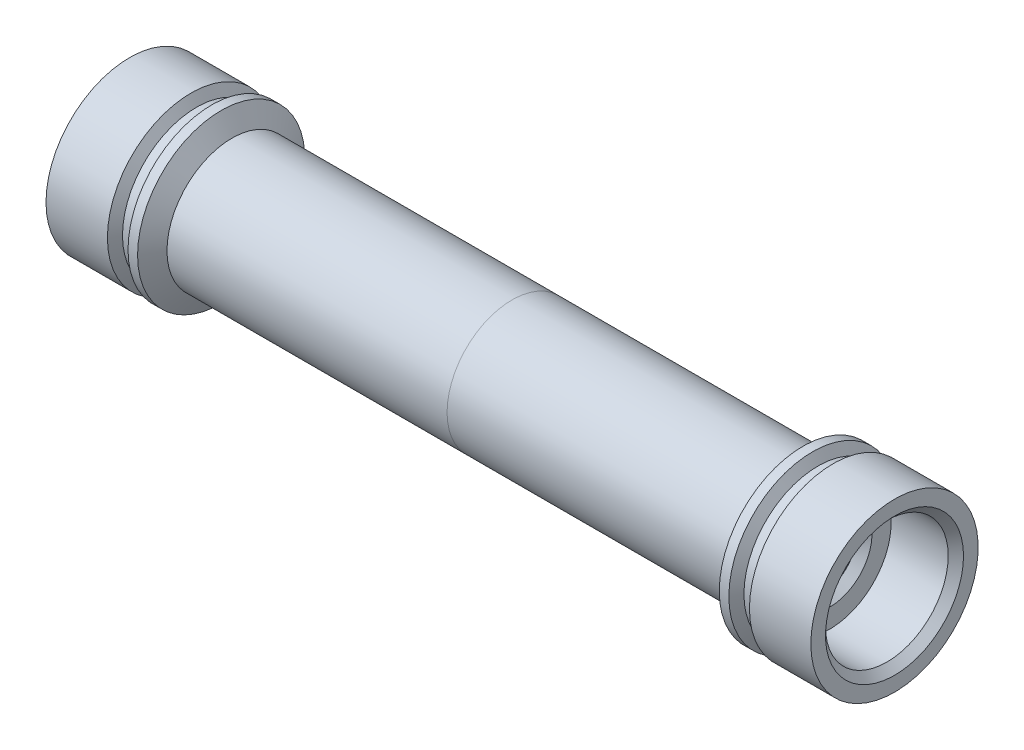
SolidWorks part; units mm, degrees
ref_plane "Front Plane" through (0, 0, 0) normal (0, 0, 1) x (1, 0, 0)
ref_plane "Top Plane" through (0, 0, 0) normal (0, 1, 0) x (1, 0, 0)
ref_plane "Right Plane" through (0, 0, 0) normal (1, 0, 0) x (0, 0, -1)
sketch "Sketch2" plane through (0, 0, 0) normal (0, 0, 1) x (1, 0, 0)
  line L0 (0, 0) -> (0, 28.4375) construction
  line L1 (-25.4, 4.075) -> (-21.1, 4.075) construction
  line L2 (-25.4, 4.075) -> (-25.4, -4.075) construction
  line L3 (-25.4, -4.075) -> (-21.1, -4.075) construction
  line L4 (-21.1, 4.075) -> (-21.1, -4.075) construction
  line L5 (-25.4, 4.075) -> (-21.1, -4.075) construction
  line L6 (-25.4, -4.075) -> (-21.1, 4.075) construction
  line L7 (21.1, 4.5) -> (42.4832, 4.5) construction
  line L8 (21.1, 4.5) -> (21.1, -4.5) construction
  line L9 (21.1, -4.5) -> (42.4832, -4.5) construction
  line L10 (42.4832, 4.5) -> (42.4832, -4.5) construction
  line L11 (21.1, 4.5) -> (42.4832, -4.5) construction
  line L12 (21.1, -4.5) -> (42.4832, 4.5) construction
  line L13 (-25.4, 0) -> (42.4832, 0) construction
  line L14 (-25.4, 5.5562) -> (-21.3216, 5.5562)
  line L21 (-18.6035, 4.318) -> (0, 4.318)
  line L22 (-25.4, 5.5562) -> (-25.4, 4.075)
  line L23 (-25.4, 4.075) -> (-21.1, 4.075)
  line L24 (-21.1, 4.075) -> (-21.1, 0)
  line L25 (-21.1, 0) -> (0, 0)
  line L26 (0, 0) -> (0, 4.318)
  line L27 (-30.6688, -5.5562) -> (-30.6688, 5.5562) construction
  line L28 (-21.3216, 5.5562) -> (-20.955, 4.9212)
  line L29 (-20.955, 4.9212) -> (-20.32, 4.9212)
  line L30 (-25.4, 5.5562) -> (25.4, 5.5562) construction
  line L31 (0, 1.625) -> (-12.5, 1.625)
  line L32 (-12.5, 1.625) -> (-14.125, 0)
  line L33 (-12.5, 1.625) -> (-12.5, -1.625) construction
  line L34 (-12.5, 1.625) -> (12.5, 1.625) construction
  line L35 (-21.1, 1.905) -> (-15.448, 1.905)
  line L36 (-15.448, 1.905) -> (-15.448, 0)
  line L37 (-21.1, 2.805) -> (-20.592, 2.297)
  line L38 (-15.448, 1.905) -> (-28.448, 1.905) construction
  line L39 (-15.448, 1.905) -> (-15.448, -1.905) construction
  line L40 (-15.448, -1.905) -> (-28.448, -1.905) construction
  line L41 (-28.448, 1.905) -> (-28.448, -1.905) construction
  line L42 (-20.592, 2.297) -> (-20.592, 0)
  line L46 (-20.32, 4.9212) -> (-19.9534, 5.5562)
  line L47 (-19.9534, 5.5562) -> (-19.3184, 5.5562)
  line L48 (-19.3184, 5.5562) -> (-18.6035, 4.318)
  line L49 (-20.6375, 4.9212) -> (-20.6375, 8.7882) construction
  line L50 (-20.6375, 8.7882) -> (20.6375, 8.7882) construction
  point P0 (-23.25, 0)
  point P5 (31.7916, 0)
  point P27 (-30.6688, 0)
  point P29 (-12.5, 0)
  point P33 (0, 8.7882)
  point P36 (0, 1.625)
  point P48 (-15.448, 0)
  point P51 (0, 5.5562)
  dimension "D3" = 4.318
  dimension "D4" = 11.1125
  dimension "D5" = 8.15
  dimension "D13" = 45
  dimension "D14" = 25
  dimension "D15" = 3.25
  dimension "D16" = 3.81
  dimension "D17" = 3.048
  dimension "D18" = 1.27
  dimension "D19" = 0.508
  dimension "D20" = 45
  dimension "D21" = 13
  dimension "D11" = 50.8
  dimension "D6" = 60
  dimension "D7" = 0.635
  dimension "D8" = 60
  dimension "D9" = 41.275
  dimension "D10" = 0.635
  dimension "D12" = 0.635
  dimension "D22" = 4.3
revolve "Revolve1" add sketch "Sketch2" angle 360 about L13 region at (-12.0038, 3.1274, 0)
chamfer "Chamfer1" distance 0.508 angle 45 1 edges at (-25.4, 0, 4.075)
mirror "Mirror1" about plane through (0, 0, 0) normal (1, 0, 0) of bodies 101
equation "\"D15@Sketch2\"=3mm+.25mm"
equation "\"D22@Sketch2\"=4.3mm"
